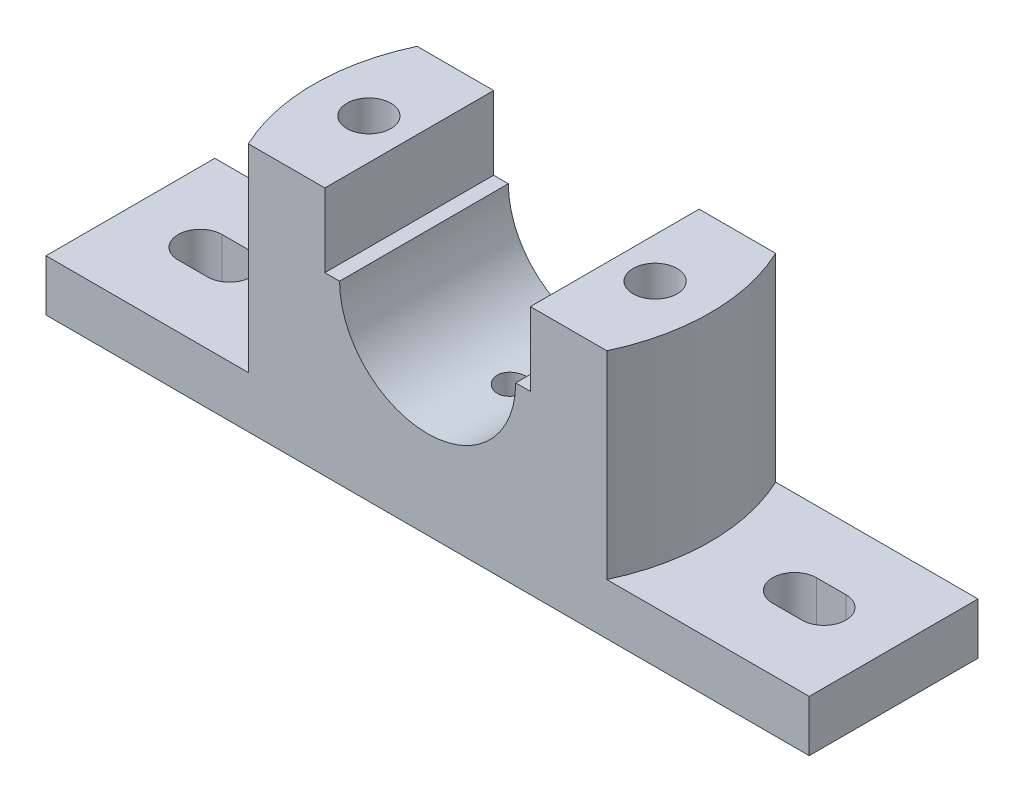
SolidWorks part; units mm, degrees
ref_plane "Front Plane" through (0, 0, 0) normal (0, 0, 1) x (1, 0, 0)
ref_plane "Top Plane" through (0, 0, 0) normal (0, 1, 0) x (1, 0, 0)
ref_plane "Right Plane" through (0, 0, 0) normal (1, 0, 0) x (0, 0, -1)
sketch "Sketch1" plane through (0, 0, 0) normal (0, 1, 0) x (1, 0, 0)
  line L0 (0, 65.2416) -> (0, -57.7026) construction
  line L1 (-104, 23) -> (104, 23)
  line L2 (-104, 23) -> (-104, -23)
  line L3 (-104, -23) -> (104, -23)
  line L4 (104, 23) -> (104, -23)
  line L5 (-104, 23) -> (104, -23) construction
  line L6 (-104, -23) -> (104, 23) construction
  line L7 (-122.9442, 0) -> (138.0223, 0) construction
  line L8 (-85, 6) -> (-77, 6)
  line L9 (-85, -6) -> (-77, -6)
  line L10 (85, -6) -> (77, -6)
  line L11 (85, 6) -> (77, 6)
  arc A0 (-85, 6) -> (-85, -6) centre (-85, 0) ccw
  arc A1 (-77, -6) -> (-77, 6) centre (-77, 0) ccw
  arc A2 (85, 6) -> (85, -6) centre (85, 0) cw
  arc A3 (77, -6) -> (77, 6) centre (77, 0) cw
  point P0 (0, 0)
  dimension "D5" = 6
  dimension "D6" = 6
  dimension "D1" = 208
  dimension "D2" = 46
  dimension "D3" = 77
  dimension "D4" = 8
extrude "Boss-Extrude1" add sketch "Sketch1" along normal blind 14
sketch "Sketch2" plane through (0, 14, 0) normal (0, 1, 0) x (1, 0, 0)
  line L0 (0, 70.2344) -> (0, -53.3782) construction
  line L1 (-140.9184, 0) -> (125.6354, 0) construction
  line L2 (-48.8569, 23) -> (48.8569, 23)
  line L3 (104, 23) -> (-104, 23) construction
  line L4 (-48.8569, -23) -> (48.8569, -23)
  arc A0 (-48.8569, 23) -> (-48.8569, -23) centre (0, 0) ccw
  arc A1 (48.8569, -23) -> (48.8569, 23) centre (0, 0) ccw
  circle A2 centre (-39, 0) radius 6
  circle A3 centre (39, 0) radius 6
  dimension "D1" = 54
  dimension "D2" = 12
  dimension "D3" = 39
extrude "Boss-Extrude2" add sketch "Sketch2" along normal blind 54
sketch "Sketch3" plane through (0, 0, 0) normal (0, -1, 0) x (1, 0, 0)
  line L0 (0, 54.9514) -> (0, -38.7694) construction
  line L2 (-53, 14) -> (-25, 14)
  line L3 (-53, 14) -> (-53, -14)
  line L4 (-53, -14) -> (-25, -14)
  line L5 (-25, 14) -> (-25, -14)
  line L6 (-53, 14) -> (-25, -14) construction
  line L7 (-53, -14) -> (-25, 14) construction
  line L8 (53, -14) -> (25, -14)
  line L9 (25, 14) -> (25, -14)
  line L10 (53, 14) -> (25, 14)
  line L11 (53, 14) -> (53, -14)
  point P3 (-39, 0)
  dimension "D1" = 28
  dimension "D2" = 28
  dimension "D3" = 39
extrude "Cut-Extrude1" cut sketch "Sketch3" against normal blind 12
sketch "Sketch4" plane through (0, 14, 0) normal (0, 1, 0) x (1, 0, 0)
  circle A0 centre (-39, 0) radius 6 construction
  circle A3 centre (39, 0) radius 6
  circle A4 centre (39, 0) radius 6
  circle A5 centre (-39, 0) radius 6
  dimension "D1" = 0
extrude "Cut-Extrude2" cut sketch "Sketch4" against normal blind 12
sketch "Sketch5" plane through (0, 0, 0) normal (0, -1, 0) x (1, 0, 0)
  line L1 (-97.5, 16.5) -> (97.5, 16.5)
  line L2 (-97.5, 16.5) -> (-97.5, -16.5)
  line L3 (-97.5, -16.5) -> (97.5, -16.5)
  line L4 (97.5, 16.5) -> (97.5, -16.5)
  line L5 (-97.5, 16.5) -> (97.5, -16.5) construction
  line L6 (-97.5, -16.5) -> (97.5, 16.5) construction
  point P0 (0, 0)
  dimension "D1" = 195
  dimension "D2" = 33
extrude "Cut-Extrude3" cut sketch "Sketch5" against normal blind 2
sketch "Sketch6" plane through (0, 0, 23) normal (0, 0, 1) x (1, 0, 0)
  line L0 (-28, 48) -> (-24, 48)
  line L1 (-48.8569, 68) -> (48.8569, 68) construction
  line L2 (-28, 68) -> (-28, 48)
  line L3 (0, 92.7722) -> (0, -15.7822)
  line L4 (28, 68) -> (28, 48)
  line L5 (24, 48) -> (28, 48)
  line L6 (-28, 68) -> (28, 68)
  arc A0 (-24, 48) -> (24, 48) centre (0, 48) ccw
  line M12 (48.8569, 68) -> (-48.8569, 68)
  dimension "D1" = 24
  dimension "D2" = 20
  dimension "D3" = 28
extrude "Cut-Extrude4" cut sketch "Sketch6" against normal through all contours L0 A0 L3 L2 M12 | L3 A0 L5 L4 M12 region at (-12.2957, 48.9799, 23) region at (12.2957, 48.9799, 23)
sketch "Sketch8" plane through (0, 2, 0) normal (0, -1, 0) x (1, 0, 0)
  circle A0 centre (0, 0) radius 4
  dimension "D1" = 8
extrude "Cut-Extrude7" cut sketch "Sketch8" against normal through all
extrude "Boss-Extrude3" add sketch "Sketch8<2>" against normal blind 16
sketch "Sketch8<2>" plane through (0, 2, 0) normal (0, -1, 0) x (1, 0, 0) same geometry as "Sketch8"
